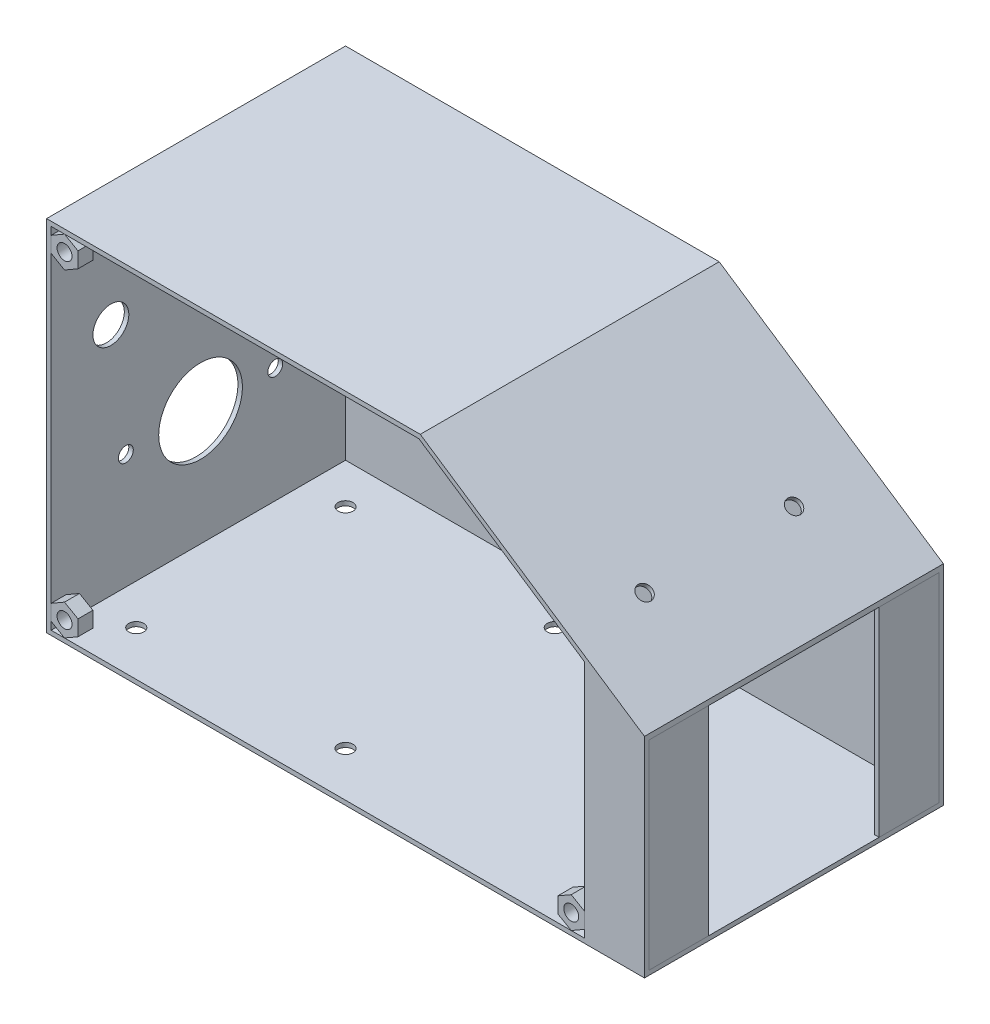
SolidWorks part; units mm, degrees
ref_plane "Front Plane" through (0, 0, 0) normal (0, 0, 1) x (1, 0, 0)
ref_plane "Top Plane" through (0, 0, 0) normal (0, 1, 0) x (1, 0, 0)
ref_plane "Right Plane" through (0, 0, 0) normal (1, 0, 0) x (0, 0, -1)
sketch "Sketch1" plane through (0, 0, 0) normal (0, 0, 1) x (1, 0, 0)
  line L0 (0, 0) -> (0, 120)
  line L1 (0, 120) -> (125, 120)
  line L2 (125, 120) -> (200, 70)
  line L3 (200, 70) -> (200, 0)
  line L4 (200, 0) -> (0, 0)
  dimension "D1" = 120
  dimension "D2" = 200
  dimension "D3" = 70
  dimension "D4" = 125
extrude "Boss-Extrude1" add sketch "Sketch1" along normal blind 100
shell "Shell1" thickness 1.5 removed face at (200, 35, 50) removed face at (105, 62, 100)
sketch "Sketch2" plane through (0, 0, 100) normal (0, 0, 1) x (1, 0, 0)
  line L0 (200, 1.5) -> (200, 68.1972)
  line L1 (200, 68.1972) -> (180, 81.5306)
  line L2 (200, 68.1972) -> (124.5458, 118.5) construction
  line L3 (180, 81.5306) -> (180, 1.5)
  line L4 (1.5, 1.5) -> (200, 1.5) construction
  line L5 (180, 1.5) -> (200, 1.5)
  dimension "D1" = 20
extrude "Boss-Extrude2" add sketch "Sketch2" against normal blind 1.5
sketch "Sketch3" plane through (200, 0, 0) normal (1, 0, 0) x (0, 0, -1)
  line L0 (-50, 70) -> (-50, 0) construction
  line L1 (-100, 70) -> (0, 70) construction
  line L2 (-100, 0) -> (0, 0) construction
  line L3 (-100, 1.5) -> (-1.5, 1.5) construction
  line L4 (-98.5, 68.1972) -> (-78.5, 68.1972)
  line L5 (-98.5, 68.1972) -> (-98.5, 1.5)
  line L6 (-98.5, 1.5) -> (-78.5, 1.5)
  line L7 (-78.5, 68.1972) -> (-78.5, 1.5)
  line L8 (-1.5, 1.5) -> (-21.5, 1.5)
  line L9 (-21.5, 68.1972) -> (-21.5, 1.5)
  line L10 (-1.5, 68.1972) -> (-21.5, 68.1972)
  line L11 (-1.5, 68.1972) -> (-1.5, 1.5)
  line M6 (-1.5, 1.5) -> (-98.5, 1.5)
  line M8 (-98.5, 68.1972) -> (-1.5, 68.1972)
  line M9 (-1.5, 68.1972) -> (-1.5, 1.5)
  dimension "D1" = 20
extrude "Boss-Extrude7" add sketch "Sketch3" against normal blind 1.5 separate body contours L9 M8 M6 M9 | L5 L4 L7 L6 region at (200, 34.8486, 11.5)
sketch "Sketch4" plane through (0, 0, 0) normal (-1, 0, 0) x (0, 0, 1)
  line L0 (50, 120) -> (50, 0) construction
  line L1 (100, 120) -> (0, 120) construction
  line L2 (100, 0) -> (0, 0) construction
  circle A0 centre (50, 40) radius 14
  circle A1 centre (20, 80) radius 6
  circle A2 centre (80, 80) radius 6
  circle A3 centre (25, 40) radius 2.5
  circle A4 centre (75, 40) radius 2.5
  circle A5 centre (50, 80) radius 6
  point P18 (0, 0)
  dimension "D1" = 28
  dimension "D2" = 12
  dimension "D3" = 60
  dimension "D7" = 5
  dimension "D8" = 40
  dimension "D4" = 40
  dimension "D5" = 40
  dimension "D6" = 25
extrude "Cut-Extrude1" cut sketch "Sketch4" against normal up to next (1.5 mm away)
sketch "Sketch5" plane through (93.8462, 140.7692, 0) normal (0.5547, 0.8321, 0) x (0.8321, -0.5547, 0)
  line L0 (37.4423, -50) -> (127.581, -50) construction
  line L1 (37.4423, -100) -> (37.4423, 0) construction
  line L2 (127.581, -100) -> (127.581, 0) construction
  circle A0 centre (97.581, -25) radius 2.5
  circle A1 centre (97.581, -75) radius 2.5
  dimension "D1" = 50
  dimension "D2" = 30
  dimension "D3" = 5
extrude "Cut-Extrude2" cut sketch "Sketch5" against normal up to next (1.5 mm away)
sketch "Sketch6" plane through (0, 0, 100) normal (0, 0, 1) x (1, 0, 0)
  line L0 (1.5, 118.5) -> (1.5, 1.5) construction
  line L1 (6, 1.5) -> (10.5, 4.0981)
  line L2 (10.5, 4.0981) -> (10.5, 9.2942)
  line L3 (10.5, 9.2942) -> (6, 11.8923)
  line L4 (6, 11.8923) -> (1.5, 9.2942)
  line L5 (1.5, 9.2942) -> (1.5, 4.0981)
  line L6 (1.5, 4.0981) -> (6, 1.5)
  line L7 (1.5, 1.5) -> (180, 1.5) construction
  line L8 (0, 60) -> (200, 60) construction
  line L9 (0, 120) -> (0, 0) construction
  line L10 (200, 0) -> (200, 70) construction
  line L11 (10.5, 115.9019) -> (10.5, 110.7058)
  line L12 (6, 118.5) -> (10.5, 115.9019)
  line L13 (1.5, 115.9019) -> (6, 118.5)
  line L14 (1.5, 110.7058) -> (1.5, 115.9019)
  line L15 (6, 108.1077) -> (1.5, 110.7058)
  line L16 (10.5, 110.7058) -> (6, 108.1077)
  line L17 (90.75, 1.5) -> (90.75, 118.5) construction
  line L18 (124.5458, 118.5) -> (1.5, 118.5) construction
  line L19 (180, 4.0981) -> (175.5, 1.5)
  line L20 (180, 9.2942) -> (180, 4.0981)
  line L21 (175.5, 11.8923) -> (180, 9.2942)
  line L22 (171, 9.2942) -> (175.5, 11.8923)
  line L23 (171, 4.0981) -> (171, 9.2942)
  line L24 (175.5, 1.5) -> (171, 4.0981)
  circle A0 centre (6, 6.6962) radius 4.5 construction
  circle A1 centre (6, 6.6962) radius 2.5
  circle A2 centre (6, 113.3038) radius 2.5
  circle A3 centre (175.5, 6.6962) radius 2.5
  point P41 (6.8923, 0)
  dimension "D1" = 5
  dimension "D2" = 6
extrude "Boss-Extrude8" add sketch "Sketch6" against normal blind 5 separate body
sketch "Sketch8" plane through (0, 0, 0) normal (0, -1, 0) x (1, 0, 0)
  line L0 (100, 100) -> (100, 0) construction
  line L1 (0, 100) -> (200, 100) construction
  line L2 (0, 0) -> (200, 0) construction
  line L3 (0, 50) -> (100, 50) construction
  line L4 (0, 100) -> (0, 0) construction
  circle A0 centre (15, 85) radius 2.5
  circle A1 centre (85, 85) radius 2.5
  circle A2 centre (15, 15) radius 2.5
  circle A3 centre (85, 15) radius 2.5
  point P18 (0, 0)
  dimension "D1" = 70
  dimension "D2" = 70
  dimension "D3" = 5
  dimension "D4" = 5
  dimension "D5" = 15
extrude "Cut-Extrude3" cut sketch "Sketch8" against normal up to next (1.5 mm away)
